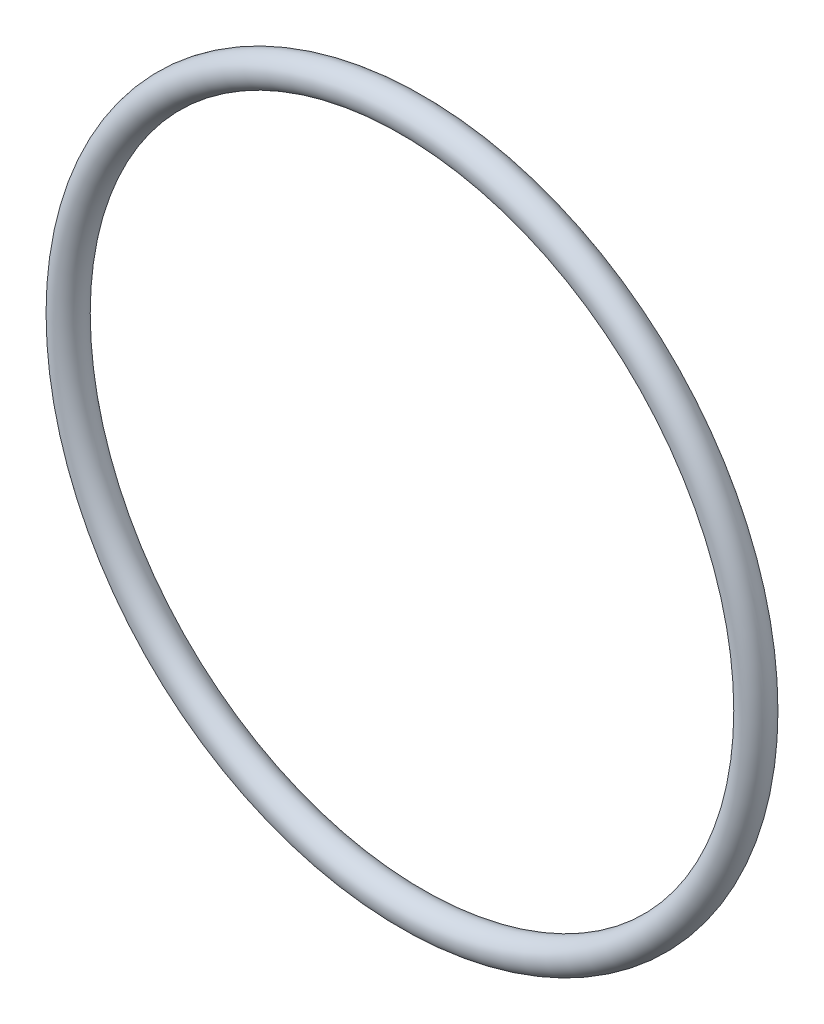
SolidWorks part; units mm, degrees
ref_plane "Front" through (0, 0, 0) normal (0, 0, 1) x (1, 0, 0)
ref_plane "Top" through (0, 0, 0) normal (0, 1, 0) x (1, 0, 0)
ref_plane "Right" through (0, 0, 0) normal (1, 0, 0) x (0, 0, -1)
sketch "Sketch1" plane through (0, 0, 0) normal (1, 0, 0) x (0, -1, 0)
  line L0 (0, -2.5) -> (0, 2.5) construction
  line L2 (-13.475, 0) -> (13.475, 0) construction
  line L3 (-52.5, 0) -> (52.5, 0) construction
  circle A0 centre (55, 0) radius 2.5
  point P9 (52.5, 0)
  point P10 (57.5, 0)
  point P13 (55, 2.5)
  point P14 (55, -2.5)
  dimension "Width" = 5
  dimension "ID" = 105
  dimension "OD" = 115
sketch "Sketch2" plane through (0, 0, 0) normal (1, 0, 0) x (0, 0, -1)
  line L0 (-2.5, 0) -> (2.5, 0) construction
  line L1 (-2.5, 0) -> (2.5, 0) construction
  circle A0 centre (0, -55) radius 2.5 construction
  circle A1 centre (0, -55) radius 2.5
revolve "Revolve1" add sketch "Sketch2" angle 360 about L1
